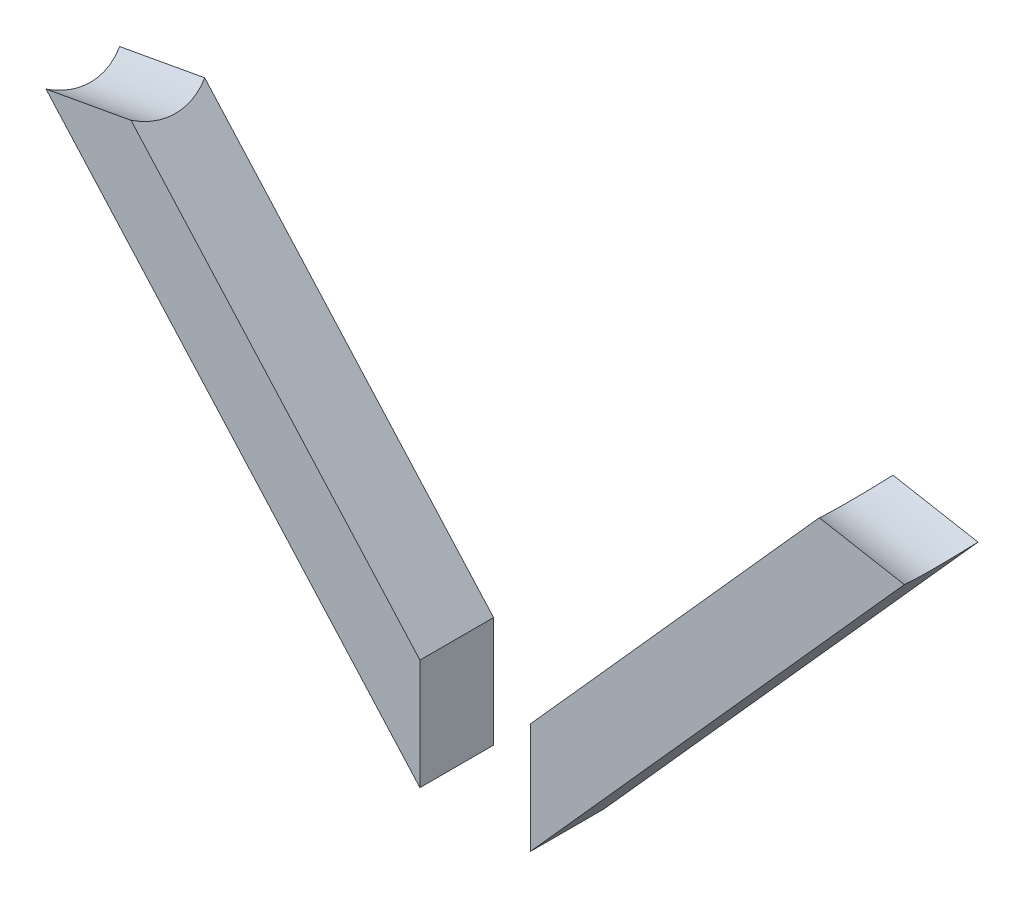
SolidWorks part; units mm, degrees
ref_plane "Front Plane" through (0, 0, 0) normal (0, 0, 1) x (1, 0, 0)
ref_plane "Top Plane" through (0, 0, 0) normal (0, 1, 0) x (1, 0, 0)
ref_plane "Right Plane" through (0, 0, 0) normal (1, 0, 0) x (0, 0, -1)
sketch "Sketch1" plane through (0, 0, 0) normal (0, 0, 1) x (1, 0, 0)
  line L0 (-155.0776, 31.8487) -> (-140.4206, 34.5116) construction
  line L1 (-82.4106, 146.7146) -> (-82.4106, -9.7593) construction
  line L2 (-91.9356, -38.7462) -> (-91.9356, -19.6962)
  line L4 (-140.4206, 34.5116) -> (-91.9356, -19.6962)
  line L5 (-155.0776, 31.8487) -> (-91.9356, -38.7462)
  line L11 (-140.4206, 34.5116) -> (-161.4207, 57.9905)
  line L12 (-161.4207, 57.9905) -> (-176.0777, 55.3275)
  line L14 (-155.0776, 31.8487) -> (-176.0777, 55.3275)
extrude "Boss-Extrude1" add sketch "Sketch1" along normal blind 6.35 and the other way blind 6.35
sketch "Sketch5" plane through (0, 0, -6.35) normal (0, 0, -1) x (-1, 0, 0)
  line L0 (140.4206, 34.5116) -> (155.0776, 31.8487) construction
sketch "Sketch6" plane through (-60.8625, -54.4371, 0) normal (0.7454, 0.6667, 0) x (0, 0, -1)
  line L0 (6.35, 119.3372) -> (0, 119.3372) construction
  line L1 (6.35, 119.3372) -> (6.35, 127.1237) construction
  line L2 (6.35, 46.6097) -> (6.35, 150.8373) construction
  line L3 (0, 127.1237) -> (0, 32.4107) construction
ref_plane "Plane5" through (-10.557, 58.1059, 0) normal (-0.1788, 0.9839, 0) x (0.9839, 0.1788, 0)
ref_plane "Plane6" through (-129.8636, -23.5943, 0) normal (-0.9839, -0.1788, 0) x (0, 0, 1)
sketch "Sketch7" plane through (-129.8636, -23.5943, 0) normal (-0.9839, -0.1788, 0) x (0, 0, 1)
  line L0 (0, 59.0572) -> (0, 71.7572) construction
  line L1 (0, 159.0831) -> (0, 5.1296) construction
  circle A0 centre (0, 71.7572) radius 12.7
extrude "Cut-Extrude2" cut sketch "Sketch7" against normal blind 50.8 and the other way blind 50.8 body kept at (-91.9356, -38.7462, 6.35)
ref_plane "Plane7" through (-82.4106, 0, 0) normal (1, 0, 0) x (0, 0, -1)
mirror "Mirror6" about plane through (-82.4106, 0, 0) normal (1, 0, 0) of bodies 106 111
